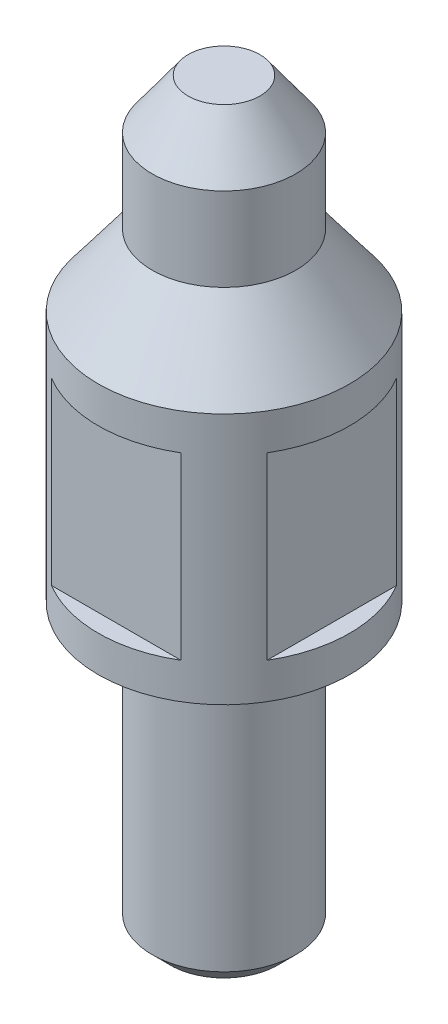
SolidWorks part; units mm, degrees
ref_plane "Front" through (0, 0, 0) normal (0, 0, 1) x (1, 0, 0)
ref_plane "Top" through (0, 0, 0) normal (0, 1, 0) x (1, 0, 0)
ref_plane "Right" through (0, 0, 0) normal (1, 0, 0) x (0, 0, -1)
sketch "Sketch1" plane through (0, 0, 0) normal (0, 0, 1) x (1, 0, 0)
  line L0 (0, -11.0826) -> (0, 21.4561) construction
  line L1 (0, -8) -> (2, -8)
  line L2 (2, -8) -> (2, 0)
  line L3 (2, 0) -> (3.5, 0)
  line L4 (3.5, 0) -> (3.5, 9)
  line L5 (3.5, 9) -> (2, 9)
  line L6 (2, 9) -> (2, 12.7)
  line L7 (2, 12.7) -> (0, 12.7)
  line L8 (0, 12.7) -> (0, -8)
  dimension "D1" = 4
  dimension "D2" = 8
  dimension "D3" = 7
  dimension "D4" = 17
  dimension "D5" = 20.7
revolve "Revolve1" add sketch "Sketch1" angle 360 about L0
cosmetic thread "Cosmetic Thread1" parameters "D1"=5, "D2"=3.22
sketch "Sketch2" plane through (0, 0, 0) normal (0, 0, 1) x (1, 0, 0)
  line L0 (-3.5, 9) -> (-3.5, 0) construction
  line L1 (-3.5, 6) -> (-3, 6)
  line L2 (-3.5, 6) -> (-3.5, 1)
  line L3 (-3.5, 1) -> (-3, 1)
  line L4 (-3, 6) -> (-3, 1)
  line L5 (3.5, 0) -> (3.5, 9) construction
  line L6 (3.5, 6) -> (3, 6)
  line L7 (3.5, 6) -> (3.5, 1)
  line L8 (3.5, 1) -> (3, 1)
  line L9 (3, 6) -> (3, 1)
  line L10 (0, -0.7192) -> (0, 21.2309) construction
  line L11 (-2, -8) -> (2, -8) construction
  dimension "D1" = 6
  dimension "D2" = 9
  dimension "D3" = 5
extrude "Cut-Extrude1" cut sketch "Sketch2" against normal through all and the other way through all
pattern_circular "CirPattern1" count 2 every 90 about axis through (0, -11.0826, 0) along (0, -1, 0) of "Cut-Extrude1"
chamfer "Chamfer1" distance 1.5 angle 53 1 edges at (0, 9, -3.5) first distance on face at (0, 9, -2)
chamfer "Chamfer2" distance 1 angle 54 1 edges at (0, 12.7, -2) first distance on face at (0, 12.7, -2)
chamfer "Chamfer3" distance 0.5 angle 45 1 edges at (0, -8, -2)
